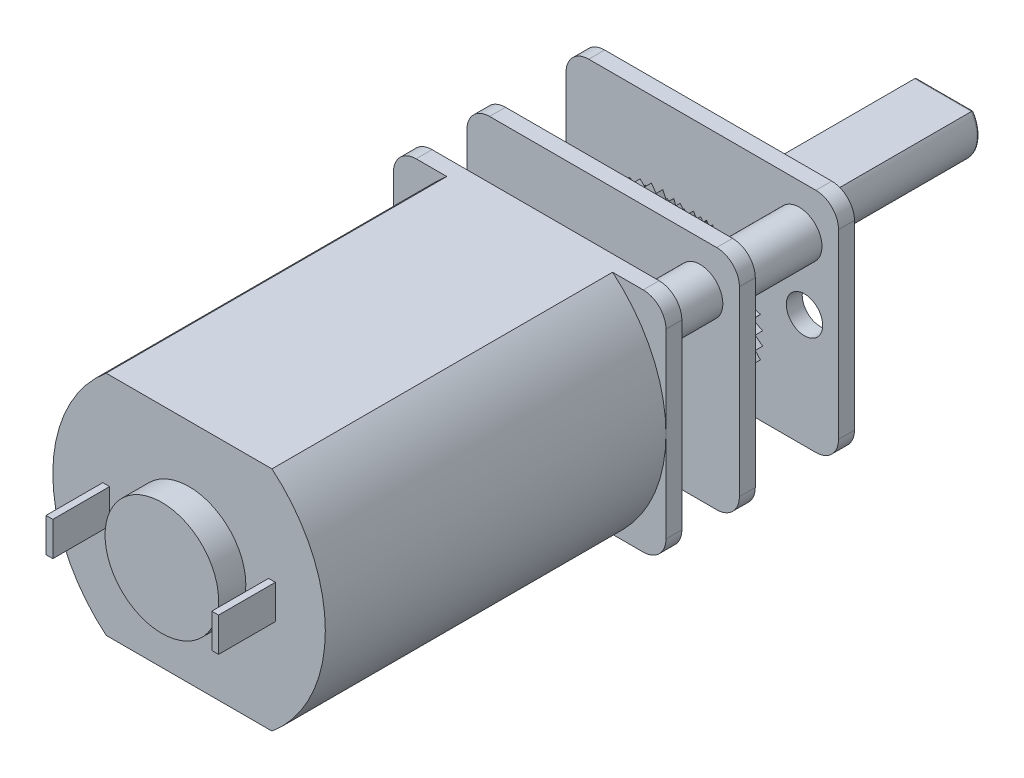
SolidWorks part; units mm, degrees
ref_plane "Front Plane" through (0, 0, 0) normal (0, 0, 1) x (1, 0, 0)
ref_plane "Top Plane" through (0, 0, 0) normal (0, 1, 0) x (1, 0, 0)
ref_plane "Right Plane" through (0, 0, 0) normal (1, 0, 0) x (0, 0, -1)
sketch "Sketch1" plane through (0, 0, 0) normal (0, 0, 1) x (1, 0, 0)
  line L0 (-1.25, 0.8292) -> (1.25, 0.8292)
  arc A0 (-1.25, 0.8292) -> (1.25, 0.8292) centre (0, 0) ccw
  dimension "D1" = 3
  dimension "D2" = 2.5
extrude "Boss-Extrude1" add sketch "Sketch1" along normal blind 9.3
sketch "Sketch2" plane through (0, 0, 9.3) normal (0, 0, 1) x (1, 0, 0)
  circle A0 centre (0, 0) radius 2
  dimension "D1" = 4
extrude "Boss-Extrude2" add sketch "Sketch2" along normal blind 0.7
sketch "Sketch3" plane through (0, 0, 10) normal (0, 0, 1) x (1, 0, 0)
  line L1 (-6, -5) -> (6, -5)
  line L2 (-6, -5) -> (-6, 5)
  line L3 (-6, 5) -> (6, 5)
  line L4 (6, -5) -> (6, 5)
  line L5 (-6, -5) -> (6, 5) construction
  line L6 (-6, 5) -> (6, -5) construction
  point P0 (0, 0)
  dimension "D1" = 12
  dimension "D2" = 10
extrude "Boss-Extrude3" add sketch "Sketch3" along normal blind 0.7
sketch "Sketch4" plane through (0, 0, 10) normal (0, 0, -1) x (-1, 0, 0)
  line L0 (6, 5) -> (6, -5) construction
  line L1 (-6, -5) -> (-6, 5) construction
  line L2 (0, 0) -> (10.5662, 0) construction
  line L3 (0, 0) -> (4.4655, -3.1267) construction
  line L4 (0, 0) -> (-4.5, 0) construction
  line L5 (0, 0) -> (-4.2701, 2.99) construction
  circle A0 centre (-4.2701, 2.99) radius 1
  circle A1 centre (4.4655, -3.1267) radius 1
  circle A2 centre (-4.5, 0) radius 0.8
  circle A3 centre (4.5, 0) radius 0.8
  point P12 (6, 0)
  point P15 (-6, 0)
  dimension "D1" = 2
  dimension "D2" = 1.6
  dimension "D3" = 9
  dimension "D4" = 4.5
  dimension "D5" = 35
  dimension "D6" = 35
extrude "Cut-Extrude1" cut sketch "Sketch4" against normal through all contours A2 | A3 region at (4.5, 0, 10) region at (-4.5, 0, 10)
fillet "Fillet1" radius 1 4 edges at (6, 5, 10.35) (-6, -5, 10.35) (-6, 5, 10.35) (6, -5, 10.35)
extrude "Boss-Extrude5" add sketch "Sketch4<3>" against normal blind 7.6 contours A0 | A1
sketch "Sketch4<3>" plane through (0, 0, 10) normal (0, 0, -1) x (-1, 0, 0) same geometry as "Sketch4"
sketch "Sketch5" plane through (0, 0, 17.6) normal (0, 0, 1) x (1, 0, 0)
  line L2 (6, -4) -> (6, 4) construction
  line L3 (5, -5) -> (-5, -5)
  line L4 (5, -5) -> (-5, -5)
  line L5 (-6, 4) -> (-6, -4) construction
  line L6 (5, 5) -> (-5, 5) construction
  line L7 (6, -4) -> (6, 4)
  line L8 (-6, 4) -> (-6, -4)
  line L9 (5, 5) -> (-5, 5)
  arc A1 (-6, -4) -> (-5, -5) centre (-5, -4) ccw construction
  arc A2 (6, 4) -> (5, 5) centre (5, 4) ccw construction
  arc A3 (5, -5) -> (6, -4) centre (5, -4) ccw construction
  arc A4 (-5, 5) -> (-6, 4) centre (-5, 4) ccw construction
  arc A5 (6, 4) -> (5, 5) centre (5, 4) ccw
  arc A6 (5, -5) -> (6, -4) centre (5, -4) ccw
  arc A7 (-6, -4) -> (-5, -5) centre (-5, -4) ccw
  arc A8 (-5, 5) -> (-6, 4) centre (-5, 4) ccw
  dimension "D1" = 10
extrude "Boss-Extrude6" add sketch "Sketch5" along normal blind 0.7
sketch "Sketch6" plane through (0, 0, 18.3) normal (0, 0, 1) x (1, 0, 0)
  line L0 (5, 5) -> (-5, 5) construction
  line L1 (-3.65, -5) -> (3.65, -5)
  line L3 (-3.65, 5) -> (3.65, 5)
  arc A0 (-3.65, 5) -> (-3.65, -5) centre (0.4941, 0) ccw
  arc A1 (3.65, 5) -> (3.65, -5) centre (-0.4941, 0) cw
  point P0 (0, 0)
  point P10 (6, 0)
  point P11 (-6, 0)
  dimension "D1" = 7.3
  dimension "D2" = 0
  dimension "D4" = 10
extrude "Boss-Extrude7" add sketch "Sketch6" along normal blind 15
sketch "Sketch7" plane through (0, 0, 33.3) normal (0, 0, 1) x (1, 0, 0)
  line L1 (3.5, -0.75) -> (3.8, -0.75)
  line L2 (3.5, -0.75) -> (3.5, 0.75)
  line L3 (3.5, 0.75) -> (3.8, 0.75)
  line L4 (3.8, -0.75) -> (3.8, 0.75)
  line L5 (3.5, -0.75) -> (3.8, 0.75) construction
  line L6 (3.5, 0.75) -> (3.8, -0.75) construction
  line L7 (-3.8, -0.75) -> (-3.5, -0.75)
  line L8 (-3.8, -0.75) -> (-3.8, 0.75)
  line L9 (-3.8, 0.75) -> (-3.5, 0.75)
  line L10 (-3.5, -0.75) -> (-3.5, 0.75)
  line L11 (-3.8, -0.75) -> (-3.5, 0.75) construction
  line L12 (-3.8, 0.75) -> (-3.5, -0.75) construction
  circle A0 centre (0, 0) radius 2.5
  point P3 (3.65, 0)
  point P8 (-3.65, 0)
  dimension "D1" = 5
  dimension "D2" = 3.65
  dimension "D3" = 0.3
  dimension "D4" = 1.5
  dimension "D5" = 3.65
extrude "Boss-Extrude8" add sketch "Sketch7" along normal blind 1.2 contours A0 region at (0, 0, 33.3)
extrude "Boss-Extrude9" add sketch "Sketch7<3>" along normal blind 2.5 contours L1 L4 L3 L2 | L9 L10 L7 L8 region at (3.65, 0, 33.3)
sketch "Sketch7<3>" plane through (0, 0, 33.3) normal (0, 0, 1) x (1, 0, 0) same geometry as "Sketch7"
ref_plane "Plane1" through (0, 0, 15.0667) normal (0, 0, -1) x (-1, 0, 0)
sketch "Sketch8" plane through (0, 0, 15.0667) normal (0, 0, -1) x (-1, 0, 0)
  line L0 (5, -5) -> (-5, -5) construction
  line L1 (6, 4) -> (6, -4) construction
  line L2 (-6, -4) -> (-6, 4) construction
  line L3 (-5, 5) -> (5, 5) construction
  line L4 (5, -5) -> (-5, -5)
  line L5 (6, 4) -> (6, -4)
  line L6 (-6, -4) -> (-6, 4)
  line L7 (-5, 5) -> (5, 5)
  arc A0 (-6, -4) -> (-5, -5) centre (-5, -4) ccw construction
  arc A1 (5, -5) -> (6, -4) centre (5, -4) ccw construction
  arc A2 (6, 4) -> (5, 5) centre (5, 4) ccw construction
  arc A3 (-5, 5) -> (-6, 4) centre (-5, 4) ccw construction
  arc A4 (-6, -4) -> (-5, -5) centre (-5, -4) ccw
  arc A5 (5, -5) -> (6, -4) centre (5, -4) ccw
  arc A6 (6, 4) -> (5, 5) centre (5, 4) ccw
  arc A7 (-5, 5) -> (-6, 4) centre (-5, 4) ccw
extrude "Boss-Extrude10" add sketch "Sketch8" along normal blind 0.7
fillet "Fillet2" radius 0.1 2 edges at (0, 0.8292, 0) (0, -1.5, 0)
sketch "Sketch10" plane through (0, 0, 14.3667) normal (0, 0, -1) x (-1, 0, 0)
  line L0 (-2.3012, -0.4892) -> (-2.324, -0.9067)
  line L1 (-2.324, -0.9067) -> (-1.9395, -0.7425)
  line L2 (-1.9395, -0.7425) -> (-1.8895, -1.1576)
  line L3 (-1.8895, -1.1576) -> (-1.5393, -0.9291)
  line L4 (-1.5393, -0.9291) -> (-1.4179, -1.3293)
  line L5 (-1.4179, -1.3293) -> (-1.1127, -1.0434)
  line L6 (-1.1127, -1.0434) -> (-0.9237, -1.4164)
  line L7 (-0.9237, -1.4164) -> (-0.6728, -1.0819)
  line L8 (-0.6728, -1.0819) -> (-0.4219, -1.4164)
  line L9 (-0.4219, -1.4164) -> (-0.2329, -1.0434)
  line L10 (-0.2329, -1.0434) -> (0.0722, -1.3293)
  line L11 (0.0722, -1.3293) -> (0.1936, -0.9291)
  line L12 (0.1936, -0.9291) -> (0.5438, -1.1576)
  line L13 (0.5438, -1.1576) -> (0.5938, -0.7425)
  line L14 (0.5938, -0.7425) -> (0.9784, -0.9067)
  line L15 (0.9784, -0.9067) -> (0.9555, -0.4892)
  line L16 (0.9555, -0.4892) -> (1.3628, -0.5842)
  line L17 (1.3628, -0.5842) -> (1.2678, -0.177)
  line L18 (1.2678, -0.177) -> (1.6853, -0.1998)
  line L19 (1.6853, -0.1998) -> (1.5211, 0.1847)
  line L20 (1.5211, 0.1847) -> (1.9362, 0.2348)
  line L21 (1.9362, 0.2348) -> (1.7077, 0.585)
  line L22 (1.7077, 0.585) -> (2.1078, 0.7063)
  line L23 (2.1078, 0.7063) -> (1.822, 1.0115)
  line L24 (1.822, 1.0115) -> (2.195, 1.2005)
  line L25 (2.195, 1.2005) -> (1.8605, 1.4514)
  line L26 (1.8605, 1.4514) -> (2.195, 1.7023)
  line L27 (2.195, 1.7023) -> (1.822, 1.8913)
  line L28 (1.822, 1.8913) -> (2.1078, 2.1965)
  line L29 (2.1078, 2.1965) -> (1.7077, 2.3178)
  line L30 (1.7077, 2.3178) -> (1.9362, 2.668)
  line L31 (1.9362, 2.668) -> (1.5211, 2.7181)
  line L32 (1.5211, 2.7181) -> (1.6853, 3.1026)
  line L33 (1.6853, 3.1026) -> (1.2678, 3.0798)
  line L34 (1.2678, 3.0798) -> (1.3628, 3.487)
  line L35 (1.3628, 3.487) -> (0.9555, 3.392)
  line L36 (0.9555, 3.392) -> (0.9784, 3.8095)
  line L37 (0.9784, 3.8095) -> (0.5938, 3.6453)
  line L38 (0.5938, 3.6453) -> (0.5438, 4.0604)
  line L39 (0.5438, 4.0604) -> (0.1936, 3.8319)
  line L40 (0.1936, 3.8319) -> (0.0722, 4.2321)
  line L41 (0.0722, 4.2321) -> (-0.2329, 3.9462)
  line L42 (-0.2329, 3.9462) -> (-0.4219, 4.3192)
  line L43 (-0.4219, 4.3192) -> (-0.6728, 3.9847)
  line L44 (-0.6728, 3.9847) -> (-0.9237, 4.3192)
  line L45 (-0.9237, 4.3192) -> (-1.1127, 3.9462)
  line L46 (-1.1127, 3.9462) -> (-1.4179, 4.2321)
  line L47 (-1.4179, 4.2321) -> (-1.5393, 3.8319)
  line L48 (-1.5393, 3.8319) -> (-1.8895, 4.0604)
  line L49 (-1.8895, 4.0604) -> (-1.9395, 3.6453)
  line L50 (-1.9395, 3.6453) -> (-2.324, 3.8095)
  line L51 (-2.324, 3.8095) -> (-2.3012, 3.392)
  line L52 (-2.3012, 3.392) -> (-2.7084, 3.487)
  line L53 (-2.7084, 3.487) -> (-2.6135, 3.0798)
  line L54 (-2.6135, 3.0798) -> (-3.031, 3.1026)
  line L55 (-3.031, 3.1026) -> (-2.8667, 2.7181)
  line L56 (-2.8667, 2.7181) -> (-3.2819, 2.668)
  line L57 (-3.2819, 2.668) -> (-3.0534, 2.3178)
  line L58 (-3.0534, 2.3178) -> (-3.4535, 2.1965)
  line L59 (-3.4535, 2.1965) -> (-3.1677, 1.8913)
  line L60 (-3.1677, 1.8913) -> (-3.5406, 1.7023)
  line L61 (-3.5406, 1.7023) -> (-3.2061, 1.4514)
  line L62 (-3.2061, 1.4514) -> (-3.5406, 1.2005)
  line L63 (-3.5406, 1.2005) -> (-3.1677, 1.0115)
  line L64 (-3.1677, 1.0115) -> (-3.4535, 0.7063)
  line L65 (-3.4535, 0.7063) -> (-3.0534, 0.585)
  line L66 (-3.0534, 0.585) -> (-3.2819, 0.2348)
  line L67 (-3.2819, 0.2348) -> (-2.8667, 0.1847)
  line L68 (-2.8667, 0.1847) -> (-3.031, -0.1998)
  line L69 (-3.031, -0.1998) -> (-2.6135, -0.177)
  line L70 (-2.6135, -0.177) -> (-2.7084, -0.5842)
  line L71 (-2.7084, -0.5842) -> (-2.3012, -0.4892)
extrude "Boss-Extrude11" add sketch "Sketch10" along normal blind 1
sketch "Sketch11" plane through (0, 0, 13.3667) normal (0, 0, -1) x (-1, 0, 0)
  line L72 (-0.086, -0.1107) -> (-0.1013, -0.3909)
  line L73 (-0.1013, -0.3909) -> (0.1568, -0.2807)
  line L74 (0.1568, -0.2807) -> (0.1904, -0.5593)
  line L75 (0.1904, -0.5593) -> (0.4254, -0.4059)
  line L76 (0.4254, -0.4059) -> (0.5068, -0.6744)
  line L77 (0.5068, -0.6744) -> (0.7116, -0.4826)
  line L78 (0.7116, -0.4826) -> (0.8384, -0.7329)
  line L79 (0.8384, -0.7329) -> (1.0068, -0.5084)
  line L80 (1.0068, -0.5084) -> (1.1752, -0.7329)
  line L81 (1.1752, -0.7329) -> (1.302, -0.4826)
  line L82 (1.302, -0.4826) -> (1.5068, -0.6744)
  line L83 (1.5068, -0.6744) -> (1.5882, -0.4059)
  line L84 (1.5882, -0.4059) -> (1.8232, -0.5593)
  line L85 (1.8232, -0.5593) -> (1.8568, -0.2807)
  line L86 (1.8568, -0.2807) -> (2.1149, -0.3909)
  line L87 (2.1149, -0.3909) -> (2.0996, -0.1107)
  line L88 (2.0996, -0.1107) -> (2.3728, -0.1744)
  line L89 (2.3728, -0.1744) -> (2.3091, 0.0988)
  line L90 (2.3091, 0.0988) -> (2.5893, 0.0835)
  line L91 (2.5893, 0.0835) -> (2.4791, 0.3416)
  line L92 (2.4791, 0.3416) -> (2.7577, 0.3752)
  line L93 (2.7577, 0.3752) -> (2.6043, 0.6101)
  line L94 (2.6043, 0.6101) -> (2.8728, 0.6916)
  line L95 (2.8728, 0.6916) -> (2.681, 0.8964)
  line L96 (2.681, 0.8964) -> (2.9313, 1.0232)
  line L97 (2.9313, 1.0232) -> (2.7068, 1.1916)
  line L98 (2.7068, 1.1916) -> (2.9313, 1.36)
  line L99 (2.9313, 1.36) -> (2.681, 1.4868)
  line L100 (2.681, 1.4868) -> (2.8728, 1.6916)
  line L101 (2.8728, 1.6916) -> (2.6043, 1.773)
  line L102 (2.6043, 1.773) -> (2.7577, 2.008)
  line L103 (2.7577, 2.008) -> (2.4791, 2.0416)
  line L104 (2.4791, 2.0416) -> (2.5893, 2.2997)
  line L105 (2.5893, 2.2997) -> (2.3091, 2.2844)
  line L106 (2.3091, 2.2844) -> (2.3728, 2.5576)
  line L107 (2.3728, 2.5576) -> (2.0996, 2.4939)
  line L108 (2.0996, 2.4939) -> (2.1149, 2.7741)
  line L109 (2.1149, 2.7741) -> (1.8568, 2.6639)
  line L110 (1.8568, 2.6639) -> (1.8232, 2.9424)
  line L111 (1.8232, 2.9424) -> (1.5882, 2.7891)
  line L112 (1.5882, 2.7891) -> (1.5068, 3.0576)
  line L113 (1.5068, 3.0576) -> (1.302, 2.8658)
  line L114 (1.302, 2.8658) -> (1.1752, 3.1161)
  line L115 (1.1752, 3.1161) -> (1.0068, 2.8916)
  line L116 (1.0068, 2.8916) -> (0.8384, 3.1161)
  line L117 (0.8384, 3.1161) -> (0.7116, 2.8658)
  line L118 (0.7116, 2.8658) -> (0.5068, 3.0576)
  line L119 (0.5068, 3.0576) -> (0.4254, 2.7891)
  line L120 (0.4254, 2.7891) -> (0.1904, 2.9424)
  line L121 (0.1904, 2.9424) -> (0.1568, 2.6639)
  line L122 (0.1568, 2.6639) -> (-0.1013, 2.7741)
  line L123 (-0.1013, 2.7741) -> (-0.086, 2.4939)
  line L124 (-0.086, 2.4939) -> (-0.3592, 2.5576)
  line L125 (-0.3592, 2.5576) -> (-0.2955, 2.2844)
  line L126 (-0.2955, 2.2844) -> (-0.5757, 2.2997)
  line L127 (-0.5757, 2.2997) -> (-0.4655, 2.0416)
  line L128 (-0.4655, 2.0416) -> (-0.7441, 2.008)
  line L129 (-0.7441, 2.008) -> (-0.5907, 1.773)
  line L130 (-0.5907, 1.773) -> (-0.8592, 1.6916)
  line L131 (-0.8592, 1.6916) -> (-0.6674, 1.4868)
  line L132 (-0.6674, 1.4868) -> (-0.9177, 1.36)
  line L133 (-0.9177, 1.36) -> (-0.6932, 1.1916)
  line L134 (-0.6932, 1.1916) -> (-0.9177, 1.0232)
  line L135 (-0.9177, 1.0232) -> (-0.6674, 0.8964)
  line L136 (-0.6674, 0.8964) -> (-0.8592, 0.6916)
  line L137 (-0.8592, 0.6916) -> (-0.5907, 0.6101)
  line L138 (-0.5907, 0.6101) -> (-0.7441, 0.3752)
  line L139 (-0.7441, 0.3752) -> (-0.4655, 0.3416)
  line L140 (-0.4655, 0.3416) -> (-0.5757, 0.0835)
  line L141 (-0.5757, 0.0835) -> (-0.2955, 0.0988)
  line L142 (-0.2955, 0.0988) -> (-0.3592, -0.1744)
  line L143 (-0.3592, -0.1744) -> (-0.086, -0.1107)
  point P72 (0, 0)
extrude "Boss-Extrude12" add sketch "Sketch11" along normal blind 1
sketch "Sketch12" plane through (0, 0, 12.3667) normal (0, 0, -1) x (-1, 0, 0)
  line L144 (-1.8844, -3.4142) -> (-1.9109, -3.9003)
  line L145 (-1.9109, -3.9003) -> (-1.4632, -3.7091)
  line L146 (-1.4632, -3.7091) -> (-1.4049, -4.1925)
  line L147 (-1.4049, -4.1925) -> (-0.9971, -3.9264)
  line L148 (-0.9971, -3.9264) -> (-0.8558, -4.3924)
  line L149 (-0.8558, -4.3924) -> (-0.5004, -4.0595)
  line L150 (-0.5004, -4.0595) -> (-0.2803, -4.4938)
  line L151 (-0.2803, -4.4938) -> (0.0118, -4.1043)
  line L152 (0.0118, -4.1043) -> (0.304, -4.4938)
  line L153 (0.304, -4.4938) -> (0.5241, -4.0595)
  line L154 (0.5241, -4.0595) -> (0.8794, -4.3924)
  line L155 (0.8794, -4.3924) -> (1.0208, -3.9264)
  line L156 (1.0208, -3.9264) -> (1.4285, -4.1925)
  line L157 (1.4285, -4.1925) -> (1.4868, -3.7091)
  line L158 (1.4868, -3.7091) -> (1.9346, -3.9003)
  line L159 (1.9346, -3.9003) -> (1.908, -3.4142)
  line L160 (1.908, -3.4142) -> (2.3822, -3.5247)
  line L161 (2.3822, -3.5247) -> (2.2716, -3.0506)
  line L162 (2.2716, -3.0506) -> (2.7578, -3.0771)
  line L163 (2.7578, -3.0771) -> (2.5665, -2.6294)
  line L164 (2.5665, -2.6294) -> (3.05, -2.5711)
  line L165 (3.05, -2.5711) -> (2.7839, -2.1633)
  line L166 (2.7839, -2.1633) -> (3.2498, -2.022)
  line L167 (3.2498, -2.022) -> (2.9169, -1.6666)
  line L168 (2.9169, -1.6666) -> (3.3513, -1.4465)
  line L169 (3.3513, -1.4465) -> (2.9618, -1.1544)
  line L170 (2.9618, -1.1544) -> (3.3513, -0.8622)
  line L171 (3.3513, -0.8622) -> (2.9169, -0.6421)
  line L172 (2.9169, -0.6421) -> (3.2498, -0.2868)
  line L173 (3.2498, -0.2868) -> (2.7839, -0.1454)
  line L174 (2.7839, -0.1454) -> (3.05, 0.2623)
  line L175 (3.05, 0.2623) -> (2.5665, 0.3206)
  line L176 (2.5665, 0.3206) -> (2.7578, 0.7684)
  line L177 (2.7578, 0.7684) -> (2.2716, 0.7418)
  line L178 (2.2716, 0.7418) -> (2.3822, 1.216)
  line L179 (2.3822, 1.216) -> (1.908, 1.1054)
  line L180 (1.908, 1.1054) -> (1.9346, 1.5916)
  line L181 (1.9346, 1.5916) -> (1.4868, 1.4004)
  line L182 (1.4868, 1.4004) -> (1.4285, 1.8838)
  line L183 (1.4285, 1.8838) -> (1.0208, 1.6177)
  line L184 (1.0208, 1.6177) -> (0.8794, 2.0836)
  line L185 (0.8794, 2.0836) -> (0.5241, 1.7508)
  line L186 (0.5241, 1.7508) -> (0.304, 2.1851)
  line L187 (0.304, 2.1851) -> (0.0118, 1.7956)
  line L188 (0.0118, 1.7956) -> (-0.2803, 2.1851)
  line L189 (-0.2803, 2.1851) -> (-0.5004, 1.7508)
  line L190 (-0.5004, 1.7508) -> (-0.8558, 2.0836)
  line L191 (-0.8558, 2.0836) -> (-0.9971, 1.6177)
  line L192 (-0.9971, 1.6177) -> (-1.4049, 1.8838)
  line L193 (-1.4049, 1.8838) -> (-1.4632, 1.4004)
  line L194 (-1.4632, 1.4004) -> (-1.9109, 1.5916)
  line L195 (-1.9109, 1.5916) -> (-1.8844, 1.1054)
  line L196 (-1.8844, 1.1054) -> (-2.3586, 1.216)
  line L197 (-2.3586, 1.216) -> (-2.248, 0.7418)
  line L198 (-2.248, 0.7418) -> (-2.7342, 0.7684)
  line L199 (-2.7342, 0.7684) -> (-2.5429, 0.3206)
  line L200 (-2.5429, 0.3206) -> (-3.0263, 0.2623)
  line L201 (-3.0263, 0.2623) -> (-2.7602, -0.1454)
  line L202 (-2.7602, -0.1454) -> (-3.2262, -0.2868)
  line L203 (-3.2262, -0.2868) -> (-2.8933, -0.6421)
  line L204 (-2.8933, -0.6421) -> (-3.3276, -0.8622)
  line L205 (-3.3276, -0.8622) -> (-2.9381, -1.1544)
  line L206 (-2.9381, -1.1544) -> (-3.3276, -1.4465)
  line L207 (-3.3276, -1.4465) -> (-2.8933, -1.6666)
  line L208 (-2.8933, -1.6666) -> (-3.2262, -2.022)
  line L209 (-3.2262, -2.022) -> (-2.7602, -2.1633)
  line L210 (-2.7602, -2.1633) -> (-3.0263, -2.5711)
  line L211 (-3.0263, -2.5711) -> (-2.5429, -2.6294)
  line L212 (-2.5429, -2.6294) -> (-2.7342, -3.0771)
  line L213 (-2.7342, -3.0771) -> (-2.248, -3.0506)
  line L214 (-2.248, -3.0506) -> (-2.3586, -3.5247)
  line L215 (-2.3586, -3.5247) -> (-1.8844, -3.4142)
extrude "Boss-Extrude13" add sketch "Sketch12" along normal blind 1
sketch "Sketch13" plane through (0, 0, 11.3667) normal (0, 0, -1) x (-1, 0, 0)
  line L72 (-0.936, -1.1377) -> (-0.9483, -1.3629)
  line L73 (-0.9483, -1.3629) -> (-0.7408, -1.2743)
  line L74 (-0.7408, -1.2743) -> (-0.7138, -1.4983)
  line L75 (-0.7138, -1.4983) -> (-0.5249, -1.375)
  line L76 (-0.5249, -1.375) -> (-0.4594, -1.5909)
  line L77 (-0.4594, -1.5909) -> (-0.2948, -1.4367)
  line L78 (-0.2948, -1.4367) -> (-0.1928, -1.6379)
  line L79 (-0.1928, -1.6379) -> (-0.0575, -1.4574)
  line L80 (-0.0575, -1.4574) -> (0.0779, -1.6379)
  line L81 (0.0779, -1.6379) -> (0.1799, -1.4367)
  line L82 (0.1799, -1.4367) -> (0.3445, -1.5909)
  line L83 (0.3445, -1.5909) -> (0.41, -1.375)
  line L84 (0.41, -1.375) -> (0.5989, -1.4983)
  line L85 (0.5989, -1.4983) -> (0.6259, -1.2743)
  line L86 (0.6259, -1.2743) -> (0.8334, -1.3629)
  line L87 (0.8334, -1.3629) -> (0.821, -1.1377)
  line L88 (0.821, -1.1377) -> (1.0407, -1.1889)
  line L89 (1.0407, -1.1889) -> (0.9895, -0.9692)
  line L90 (0.9895, -0.9692) -> (1.2148, -0.9815)
  line L91 (1.2148, -0.9815) -> (1.1262, -0.7741)
  line L92 (1.1262, -0.7741) -> (1.3501, -0.7471)
  line L93 (1.3501, -0.7471) -> (1.2268, -0.5582)
  line L94 (1.2268, -0.5582) -> (1.4427, -0.4927)
  line L95 (1.4427, -0.4927) -> (1.2885, -0.3281)
  line L96 (1.2885, -0.3281) -> (1.4897, -0.2261)
  line L97 (1.4897, -0.2261) -> (1.3093, -0.0907)
  line L98 (1.3093, -0.0907) -> (1.4897, 0.0446)
  line L99 (1.4897, 0.0446) -> (1.2885, 0.1466)
  line L100 (1.2885, 0.1466) -> (1.4427, 0.3113)
  line L101 (1.4427, 0.3113) -> (1.2268, 0.3767)
  line L102 (1.2268, 0.3767) -> (1.3501, 0.5656)
  line L103 (1.3501, 0.5656) -> (1.1262, 0.5926)
  line L104 (1.1262, 0.5926) -> (1.2148, 0.8001)
  line L105 (1.2148, 0.8001) -> (0.9895, 0.7878)
  line L106 (0.9895, 0.7878) -> (1.0407, 1.0075)
  line L107 (1.0407, 1.0075) -> (0.821, 0.9563)
  line L108 (0.821, 0.9563) -> (0.8334, 1.1815)
  line L109 (0.8334, 1.1815) -> (0.6259, 1.0929)
  line L110 (0.6259, 1.0929) -> (0.5989, 1.3169)
  line L111 (0.5989, 1.3169) -> (0.41, 1.1936)
  line L112 (0.41, 1.1936) -> (0.3445, 1.4095)
  line L113 (0.3445, 1.4095) -> (0.1799, 1.2552)
  line L114 (0.1799, 1.2552) -> (0.0779, 1.4565)
  line L115 (0.0779, 1.4565) -> (-0.0575, 1.276)
  line L116 (-0.0575, 1.276) -> (-0.1928, 1.4565)
  line L117 (-0.1928, 1.4565) -> (-0.2948, 1.2552)
  line L118 (-0.2948, 1.2552) -> (-0.4594, 1.4095)
  line L119 (-0.4594, 1.4095) -> (-0.5249, 1.1936)
  line L120 (-0.5249, 1.1936) -> (-0.7138, 1.3169)
  line L121 (-0.7138, 1.3169) -> (-0.7408, 1.0929)
  line L122 (-0.7408, 1.0929) -> (-0.9483, 1.1815)
  line L123 (-0.9483, 1.1815) -> (-0.936, 0.9563)
  line L124 (-0.936, 0.9563) -> (-1.1557, 1.0075)
  line L125 (-1.1557, 1.0075) -> (-1.1044, 0.7878)
  line L126 (-1.1044, 0.7878) -> (-1.3297, 0.8001)
  line L127 (-1.3297, 0.8001) -> (-1.2411, 0.5926)
  line L128 (-1.2411, 0.5926) -> (-1.4651, 0.5656)
  line L129 (-1.4651, 0.5656) -> (-1.3418, 0.3767)
  line L130 (-1.3418, 0.3767) -> (-1.5576, 0.3113)
  line L131 (-1.5576, 0.3113) -> (-1.4034, 0.1466)
  line L132 (-1.4034, 0.1466) -> (-1.6047, 0.0446)
  line L133 (-1.6047, 0.0446) -> (-1.4242, -0.0907)
  line L134 (-1.4242, -0.0907) -> (-1.6047, -0.2261)
  line L135 (-1.6047, -0.2261) -> (-1.4034, -0.3281)
  line L136 (-1.4034, -0.3281) -> (-1.5576, -0.4927)
  line L137 (-1.5576, -0.4927) -> (-1.3418, -0.5582)
  line L138 (-1.3418, -0.5582) -> (-1.4651, -0.7471)
  line L139 (-1.4651, -0.7471) -> (-1.2411, -0.7741)
  line L140 (-1.2411, -0.7741) -> (-1.3297, -0.9815)
  line L141 (-1.3297, -0.9815) -> (-1.1044, -0.9692)
  line L142 (-1.1044, -0.9692) -> (-1.1557, -1.1889)
  line L143 (-1.1557, -1.1889) -> (-0.936, -1.1377)
extrude "Boss-Extrude14" add sketch "Sketch13" along normal blind 0.67
sketch "Sketch14" plane through (0, 0, 17.6) normal (0, 0, -1) x (-1, 0, 0)
  circle A0 centre (-0.615, 1.2765) radius 1
  point P2 (0, 0)
  point P3 (1.4818, 1.0156)
  point P4 (-0.3092, 1.4912)
  point P5 (-0.615, 1.2765)
  dimension "D1" = 2
extrude "Boss-Extrude15" add sketch "Sketch14" along normal blind 2.5
